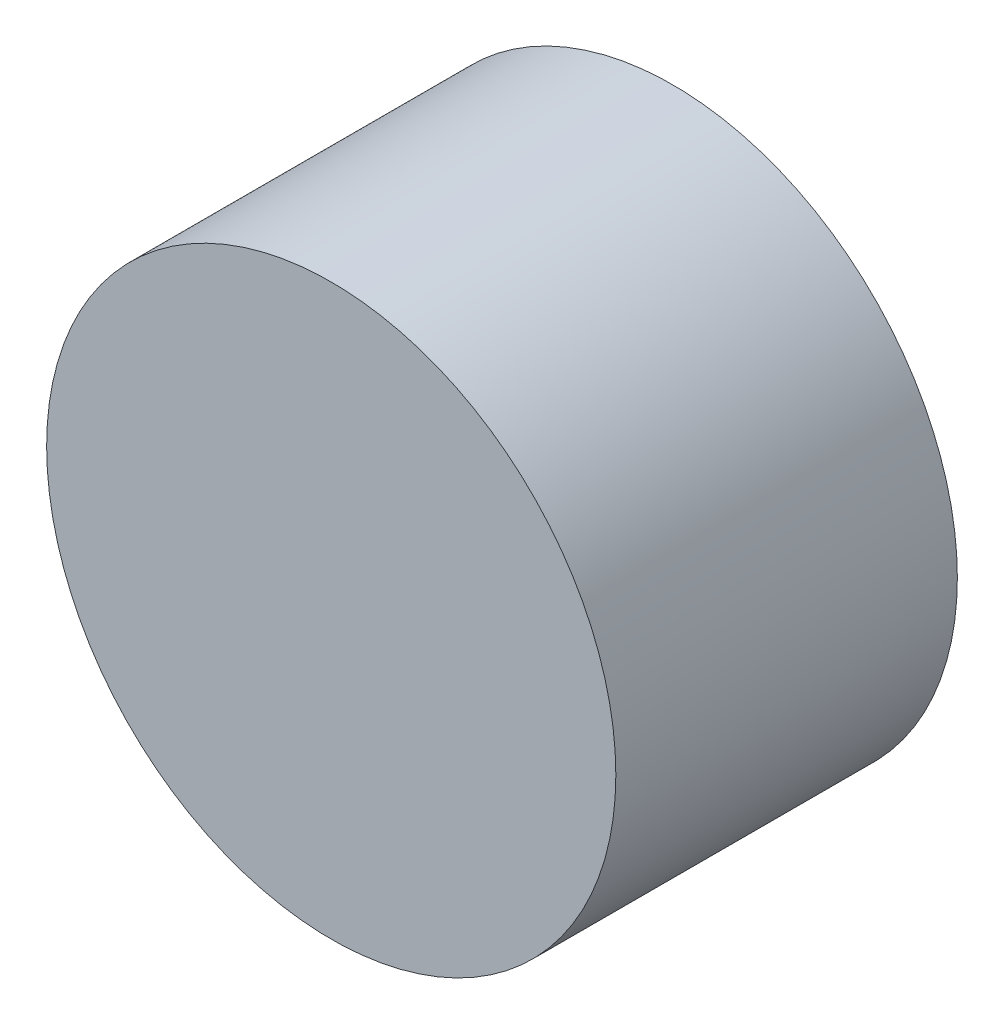
SolidWorks part; units mm, degrees
ref_plane "Front Plane" through (0, 0, 0) normal (0, 0, 1) x (1, 0, 0)
ref_plane "Top Plane" through (0, 0, 0) normal (0, 1, 0) x (1, 0, 0)
ref_plane "Right Plane" through (0, 0, 0) normal (1, 0, 0) x (0, 0, -1)
sketch "Sketch1" plane through (0, 0, 0) normal (0, 0, 1) x (1, 0, 0)
  circle A0 centre (0, 0) radius 22.5
  dimension "D1" = 45
extrude "Boss-Extrude1" add sketch "Sketch1" along normal blind 27
